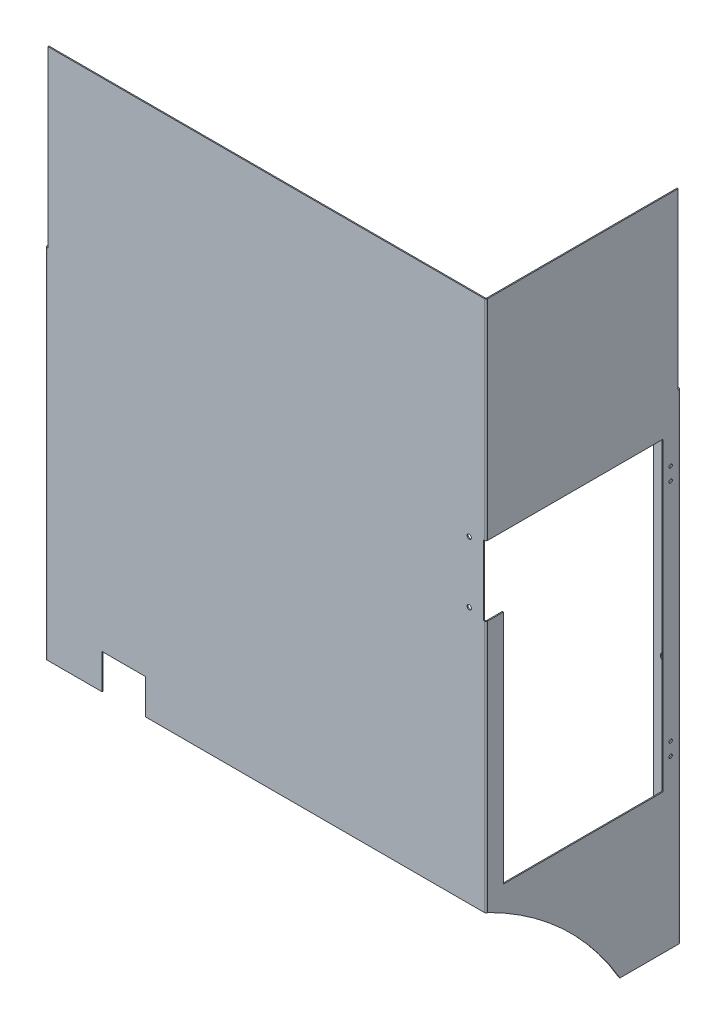
SolidWorks part; units mm, degrees
note: The reader was unsure of these and kept them because the rebuilt part matched: flange length of "Ребро-кромка1", "Ребро-кромка2", "Ребро-кромка3".
ref_plane "Спереди" through (0, 0, 0) normal (0, 0, 1) x (1, 0, 0)
ref_plane "Сверху" through (0, 0, 0) normal (0, 1, 0) x (1, 0, 0)
ref_plane "Справа" through (0, 0, 0) normal (1, 0, 0) x (0, 0, -1)
sketch "Эскиз1" plane through (0, 0, 0) normal (0, 0, 1) x (1, 0, 0)
  line L1 (0, 0) -> (505, 0)
  line L2 (0, 0) -> (0, 750)
  line L3 (0, 750) -> (505, 750)
  line L4 (505, 0) -> (505, 750)
  dimension "D1" = 750
  dimension "D3" = 505
base flange "Базовая кромка1" sketch "Эскиз1" thickness 1.2 reverse thickness direction no parameters "D1"=0.7366
edge flange "Ребро-кромка1" sketch "Эскиз8" flange angle 90 flange length 223 flange position material inside bend radius 0.7366 thickness 1.2 relief rectangular parameters "D6"=10
sketch "Эскиз8" plane through (505, 0, -1.2) normal (-1, 0, 0) x (0, 1, 0)
  line L1 (750, 0) -> (0, 0) construction
  line L2 (0, 0) -> (0, 221.8)
  line L3 (0, 221.8) -> (750, 221.8)
  line L4 (750, 221.8) -> (750, 0)
  line L5 (750, 0) -> (0, 0)
bend "EdgeBend1" bend radius 0.7366 bend angle 90 parameters "D5"=1
sketch "Эскиз9" plane through (505, 0, 0) normal (1, 0, 0) x (0, 0, -1)
  line L0 (223, 750) -> (223, 0) construction
  line L1 (1.9366, 140.7096) -> (-18.7245, 140.7096)
  line L2 (-18.7245, 140.7096) -> (-18.7245, 150.079)
  line L3 (1.9366, 750) -> (1.9366, 0) construction
  arc A0 (-18.7245, 150.079) -> (1.9366, 140.7096) centre (-157, -182.3061) ccw
  dimension "D1" = 720
  dimension "D2" = 380
extrude "Вырез-Вытянуть1" cut sketch "Эскиз9" against normal through all normal cut yes
edge flange "Ребро-кромка2" sketch "Эскиз12" flange angle 90 flange length 30 flange position material inside bend radius 0.7366 thickness 1.2 relief rectangular parameters "D6"=10
sketch "Эскиз12" plane through (503.8, 0, -223) normal (0, 0, -1) x (0, -1, 0)
  line L0 (-750, 0) -> (0, 0) construction
  line L1 (-750, 0) -> (0, 0)
  line L2 (-750, 0) -> (-750, 28.8)
  line L3 (-750, 28.8) -> (0, 28.8)
  line L4 (0, 28.8) -> (0, 0)
bend "EdgeBend2" bend radius 0.7366 bend angle 90 parameters "D5"=2
edge flange "Ребро-кромка3" sketch "Эскиз15" flange angle 90 flange length 30 flange position material inside bend radius 0.7366 thickness 1.2 relief rectangular parameters "D6"=10
sketch "Эскиз15" plane through (0, 0, -1.2) normal (-1, 0, 0) x (0, 1, 0)
  line L2 (140.7096, 0) -> (140.7096, 28.8)
  line L3 (140.7096, 28.8) -> (750, 28.8)
  line L4 (750, 28.8) -> (750, 0)
  line L5 (750, 0) -> (140.7096, 0) construction
  line L6 (750, 0) -> (140.7096, 0)
bend "EdgeBend3" bend radius 0.7366 bend angle 90 parameters "D5"=3
sketch "Эскиз16" plane through (505, 0, 0) normal (1, 0, 0) x (0, 0, -1)
  line L0 (223, 750) -> (1.2, 750) construction
  line L1 (220, 750) -> (261.4753, 750)
  line L2 (220, 750) -> (220, 550)
  line L3 (220, 550) -> (261.4753, 550)
  line L4 (261.4753, 750) -> (261.4753, 550)
  line L5 (223, 0) -> (223, 750) construction
  dimension "D1" = 3
  dimension "D2" = 200
extrude "Вырез-Вытянуть2" cut sketch "Эскиз16" against normal through all normal cut yes
sketch "Эскиз17" plane through (0, 0, 0) normal (0, 0, 1) x (1, 0, 0)
  line L0 (0, 750) -> (505, 750) construction
  line L1 (3, 750) -> (-32.5473, 750)
  line L2 (3, 750) -> (3, 550)
  line L3 (3, 550) -> (-32.5473, 550)
  line L4 (-32.5473, 750) -> (-32.5473, 550)
  line L5 (0, 750) -> (0, 140.7096) construction
  dimension "D1" = 3
  dimension "D2" = 200
extrude "Вырез-Вытянуть3" cut sketch "Эскиз17" against normal through all normal cut yes
chamfer "Фаска1" distance 10 angle 45 4 edges at (0.6, 140.7096, -30) (475, 0, -222.4) (475, 550, -222.4) (0.6, 550, -30)
sketch "Эскиз19" plane through (505, 0, 0) normal (1, 0, 0) x (0, 0, -1)
  line L0 (0, 140.7096) -> (0, 750) construction
  line L1 (20, 510) -> (203, 510)
  line L2 (20, 510) -> (20, 160)
  line L3 (20, 160) -> (203, 160)
  line L4 (203, 510) -> (203, 160)
  line L5 (223, 0) -> (223, 550) construction
  line L6 (221.0634, 0) -> (153.4263, 0) construction
  dimension "D1" = 20
  dimension "D2" = 20
  dimension "D3" = 160
  dimension "D4" = 350
extrude "Вырез-Вытянуть4" cut sketch "Эскиз19" against normal blind 10 normal cut yes
sketch "Эскиз20" plane through (505, 0, 0) normal (1, 0, 0) x (0, 0, -1)
  line L0 (0, 140.7096) -> (0, 750) construction
  line L1 (20, 510) -> (0, 510)
  line L2 (20, 510) -> (20, 430)
  line L3 (20, 430) -> (0, 430)
  line L4 (0, 510) -> (0, 430)
  dimension "D1" = 80
extrude "Вырез-Вытянуть5" cut sketch "Эскиз20" against normal blind 3 normal cut yes
sketch "Эскиз21" plane through (0, 0, 0) normal (0, 0, 1) x (1, 0, 0)
  line L0 (485.7, 505) -> (485.7, 435) construction
  line L1 (502, 470) -> (485.7, 470) construction
  line L2 (502, 510) -> (502, 430) construction
  line L3 (505, 750) -> (505, 510) construction
  circle A0 centre (485.7, 505) radius 2.5
  circle A1 centre (485.7, 435) radius 2.5
  dimension "D2" = 5
  dimension "D1" = 19.3
  dimension "D3" = 70
extrude "Вырез-Вытянуть6" cut sketch "Эскиз21" against normal up to next normal cut yes
sketch "Эскиз22" plane through (505, 0, 0) normal (1, 0, 0) x (0, 0, -1)
  line L0 (203, 510) -> (211.5, 510) construction
  line L1 (211.5, 510) -> (211.5, 160) construction
  line L2 (203, 160) -> (211.5, 160) construction
  circle A1 centre (211.5, 479) radius 2
  circle A2 centre (211.5, 464) radius 2
  circle A3 centre (211.5, 206) radius 2
  circle A4 centre (211.5, 191) radius 2
  dimension "D2" = 31
  dimension "D3" = 15
  dimension "D4" = 4
  dimension "D6" = 15
  dimension "D7" = 4
  dimension "D1" = 8.5
  dimension "D5" = 31
extrude "Вырез-Вытянуть7" cut sketch "Эскиз22" against normal up to next normal cut yes
sketch "Эскиз23" plane through (0, 0, -223) normal (0, 0, -1) x (-1, 0, 0)
  line L0 (-487, 510) -> (-487, 40) construction
  line L1 (-475, 10) -> (-475, 540) construction
  line L2 (-485, 550) -> (-503.0634, 550) construction
  line L3 (-503.0634, 0) -> (-485, 0) construction
  circle A0 centre (-487, 510) radius 4
  circle A1 centre (-487, 275) radius 4
  circle A2 centre (-487, 40) radius 4
  dimension "D4" = 8
  dimension "D5" = 8
  dimension "D6" = 8
  dimension "D1" = 12
  dimension "D2" = 40
  dimension "D3" = 40
extrude "Вырез-Вытянуть8" cut sketch "Эскиз23" against normal blind 10 normal cut yes
sketch "Эскиз24" plane through (0, 0, 0) normal (-1, 0, 0) x (0, 0, 1)
  line L0 (-18, 510) -> (-18, 180.7096) construction
  line L1 (-30, 540) -> (-30, 150.7096) construction
  line L2 (-1.9366, 550) -> (-20, 550) construction
  line L3 (-20, 140.7096) -> (-1.9366, 140.7096) construction
  circle A0 centre (-18, 510) radius 4
  circle A1 centre (-18, 345.3548) radius 4
  circle A2 centre (-18, 180.7096) radius 4
  point P12 (-10.9683, 140.7096)
  dimension "D2" = 8
  dimension "D4" = 40
  dimension "D1" = 12
  dimension "D3" = 40
extrude "Вырез-Вытянуть9" cut sketch "Эскиз24" against normal up to next normal cut yes
sketch "Эскиз25" plane through (0, 0, 0) normal (0, 0, 1) x (1, 0, 0)
  line L0 (1.9366, 140.7096) -> (503.0634, 140.7096) construction
  line L1 (65, 140.7096) -> (115, 140.7096)
  line L2 (65, 140.7096) -> (65, 180.7096)
  line L3 (65, 180.7096) -> (115, 180.7096)
  line L4 (115, 140.7096) -> (115, 180.7096)
  line L5 (0, 550) -> (0, 140.7096) construction
  dimension "D1" = 65
  dimension "D2" = 115
  dimension "D3" = 40
extrude "Вырез-Вытянуть10" cut sketch "Эскиз25" against normal blind 10 normal cut yes
sketch "Сгиб-Линии1" plane through (0, 0, 0) normal (0, 1, 0) x (1, 0, 0)
sketch "Граничная рамка1" plane through (0, 0, 0) normal (0, 1, 0) x (1, 0, 0)
sheet metal parameters "Листовой металл3" thickness 1.2 parameters "D1"=0.7366
flat pattern "Развертка3" [suppressed]
sketch "Сгиб-Линии2" plane through (0, 0, 0) normal (0, 1, 0) x (1, 0, 0)
sketch "Граничная рамка2" [suppressed] plane through (0, 0, 0) normal (0, 1, 0) x (1, 0, 0)
sheet metal parameters "Листовой металл4" thickness 1.2 parameters "D1"=0.7366
flat pattern "Развертка3" [suppressed]
sketch "Сгиб-Линии2" plane through (0, 0, 0) normal (0, 1, 0) x (1, 0, 0)
sketch "Граничная рамка2" [suppressed] plane through (0, 0, 0) normal (0, 1, 0) x (1, 0, 0)
bend of the flat pattern "Плоское состояние-<EdgeBend1>1"
sheet metal parameters "Листовой металл5" thickness 1.2 parameters "D1"=0.7366
flat pattern "Развертка3" [suppressed]
sketch "Сгиб-Линии2" plane through (0, 0, 0) normal (0, 1, 0) x (1, 0, 0)
sketch "Граничная рамка2" [suppressed] plane through (0, 0, 0) normal (0, 1, 0) x (1, 0, 0)
bend of the flat pattern "Плоское состояние-<EdgeBend1>1"
sheet metal parameters "Листовой металл6" thickness 1.2 parameters "D1"=0.7366
flat pattern "Развертка3" [suppressed]
sketch "Сгиб-Линии2" plane through (0, 0, 0) normal (0, 1, 0) x (1, 0, 0)
sketch "Граничная рамка2" [suppressed] plane through (0, 0, 0) normal (0, 1, 0) x (1, 0, 0)
bend of the flat pattern "Плоское состояние-<EdgeBend1>1"
bend of the flat pattern "Плоское состояние-<EdgeBend2>1"
sheet metal parameters "Листовой металл7" thickness 1.2 parameters "D1"=0.7366
flat pattern "Развертка3" [suppressed]
sketch "Сгиб-Линии2" plane through (0, 0, 0) normal (0, 1, 0) x (1, 0, 0)
sketch "Граничная рамка2" [suppressed] plane through (0, 0, 0) normal (0, 1, 0) x (1, 0, 0)
bend of the flat pattern "Плоское состояние-<EdgeBend1>1"
bend of the flat pattern "Плоское состояние-<EdgeBend2>1"
bend of the flat pattern "Плоское состояние-<EdgeBend3>1"
sheet metal parameters "Листовой металл8" thickness 1.2 parameters "D1"=0.7366
flat pattern "Развертка3" [suppressed]
sketch "Сгиб-Линии2" plane through (0, 0, 0) normal (0, 1, 0) x (1, 0, 0)
sketch "Граничная рамка2" [suppressed] plane through (0, 0, 0) normal (0, 1, 0) x (1, 0, 0)
bend of the flat pattern "Плоское состояние-<EdgeBend1>1"
bend of the flat pattern "Плоское состояние-<EdgeBend2>1"
bend of the flat pattern "Плоское состояние-<EdgeBend3>1"
sheet metal parameters "Листовой металл9" thickness 1.2 parameters "D1"=0.7366
flat pattern "Развертка3" [suppressed]
sketch "Сгиб-Линии2" plane through (0, 0, 0) normal (0, 1, 0) x (1, 0, 0)
sketch "Граничная рамка2" [suppressed] plane through (0, 0, 0) normal (0, 1, 0) x (1, 0, 0)
bend of the flat pattern "Плоское состояние-<EdgeBend1>1"
bend of the flat pattern "Плоское состояние-<EdgeBend2>1"
bend of the flat pattern "Плоское состояние-<EdgeBend3>1"
sheet metal parameters "Листовой металл10" thickness 1.2 parameters "D1"=0.7366
flat pattern "Развертка3" [suppressed]
sketch "Сгиб-Линии2" plane through (0, 0, 0) normal (0, 1, 0) x (1, 0, 0)
sketch "Граничная рамка2" [suppressed] plane through (0, 0, 0) normal (0, 1, 0) x (1, 0, 0)
bend of the flat pattern "Плоское состояние-<EdgeBend1>1"
bend of the flat pattern "Плоское состояние-<EdgeBend2>1"
bend of the flat pattern "Плоское состояние-<EdgeBend3>1"
sheet metal parameters "Листовой металл11" thickness 1.2 parameters "D1"=0.7366
flat pattern "Развертка3" [suppressed]
sketch "Сгиб-Линии2" plane through (0, 0, 0) normal (0, 1, 0) x (1, 0, 0)
sketch "Граничная рамка2" [suppressed] plane through (0, 0, 0) normal (0, 1, 0) x (1, 0, 0)
bend of the flat pattern "Плоское состояние-<EdgeBend1>1"
bend of the flat pattern "Плоское состояние-<EdgeBend2>1"
bend of the flat pattern "Плоское состояние-<EdgeBend3>1"
sheet metal parameters "Листовой металл12" thickness 1.2 parameters "D1"=0.7366
flat pattern "Развертка3" [suppressed]
sketch "Сгиб-Линии2" plane through (0, 0, 0) normal (0, 1, 0) x (1, 0, 0)
sketch "Граничная рамка2" [suppressed] plane through (0, 0, 0) normal (0, 1, 0) x (1, 0, 0)
bend of the flat pattern "Плоское состояние-<EdgeBend1>1"
bend of the flat pattern "Плоское состояние-<EdgeBend2>1"
bend of the flat pattern "Плоское состояние-<EdgeBend3>1"
sheet metal parameters "Листовой металл13" thickness 1.2 parameters "D1"=0.7366
flat pattern "Развертка3" [suppressed]
sketch "Сгиб-Линии2" plane through (0, 0, 0) normal (0, 1, 0) x (1, 0, 0)
sketch "Граничная рамка2" [suppressed] plane through (0, 0, 0) normal (0, 1, 0) x (1, 0, 0)
bend of the flat pattern "Плоское состояние-<EdgeBend1>1"
bend of the flat pattern "Плоское состояние-<EdgeBend2>1"
bend of the flat pattern "Плоское состояние-<EdgeBend3>1"
sheet metal parameters "Листовой металл14" thickness 1.2 parameters "D1"=0.7366
flat pattern "Развертка3" [suppressed]
sketch "Сгиб-Линии2" plane through (0, 0, 0) normal (0, 1, 0) x (1, 0, 0)
sketch "Граничная рамка2" [suppressed] plane through (0, 0, 0) normal (0, 1, 0) x (1, 0, 0)
bend of the flat pattern "Плоское состояние-<EdgeBend1>1"
bend of the flat pattern "Плоское состояние-<EdgeBend2>1"
bend of the flat pattern "Плоское состояние-<EdgeBend3>1"
sheet metal parameters "Листовой металл15" thickness 1.2 parameters "D1"=0.7366
flat pattern "Развертка3" [suppressed]
sketch "Сгиб-Линии2" plane through (0, 0, 0) normal (0, 1, 0) x (1, 0, 0)
sketch "Граничная рамка2" [suppressed] plane through (0, 0, 0) normal (0, 1, 0) x (1, 0, 0)
bend of the flat pattern "Плоское состояние-<EdgeBend1>1"
bend of the flat pattern "Плоское состояние-<EdgeBend2>1"
bend of the flat pattern "Плоское состояние-<EdgeBend3>1"
sheet metal parameters "Листовой металл16" thickness 1.2 parameters "D1"=0.7366
flat pattern "Развертка3" [suppressed]
sketch "Сгиб-Линии2" plane through (0, 0, 0) normal (0, 1, 0) x (1, 0, 0)
sketch "Граничная рамка2" [suppressed] plane through (0, 0, 0) normal (0, 1, 0) x (1, 0, 0)
bend of the flat pattern "Плоское состояние-<EdgeBend1>1"
bend of the flat pattern "Плоское состояние-<EdgeBend2>1"
bend of the flat pattern "Плоское состояние-<EdgeBend3>1"
